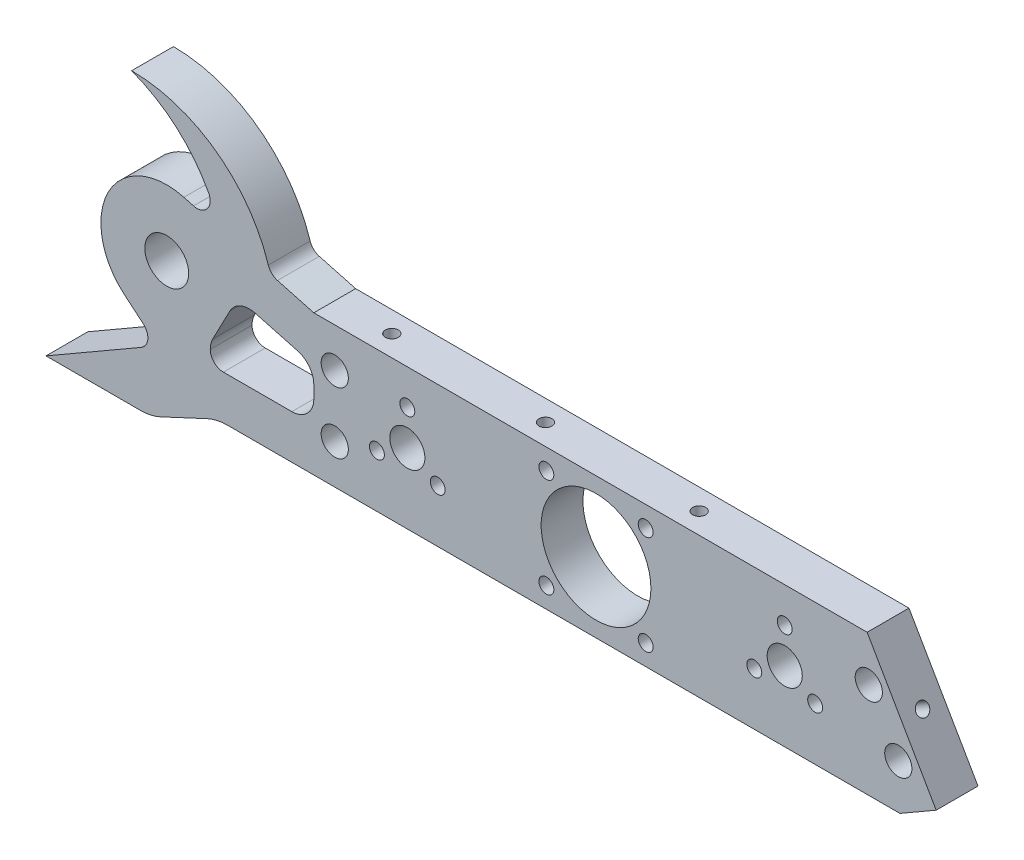
SolidWorks part; units mm, degrees
material "PE High Density"
ref_plane "Front Plane" through (0, 0, 0) normal (0, 0, 1) x (1, 0, 0)
ref_plane "Top Plane" through (0, 0, 0) normal (0, 1, 0) x (1, 0, 0)
ref_plane "Right Plane" through (0, 0, 0) normal (1, 0, 0) x (0, 0, -1)
sketch "Sketch1" plane through (0, 0, 0) normal (0, 0, 1) x (1, 0, 0)
  line L0 (-93.8686, 23.9824) -> (-64.275, 16)
  line L1 (-54.75, -16) -> (61.75, -16)
  line L2 (-54.75, -16) -> (-54.75, 16) construction
  line L3 (-54.75, 16) -> (61.75, 16)
  line L4 (61.75, -16) -> (61.75, 16)
  line L5 (-54.75, -16) -> (61.75, 16) construction
  line L6 (-54.75, 16) -> (61.75, -16) construction
  line L7 (-54.75, -16) -> (-90.7211, -16)
  line L8 (-90.7211, -16) -> (-107.4168, -1.9907)
  line L9 (-54.75, 16) -> (-64.275, 16)
  line L10 (-64.275, 16) -> (-64.275, -16) construction
  line L11 (-112.2407, -24) -> (26.8379, -24) construction
  line L12 (3.5, 0) -> (0, 0) construction
  arc A0 (-93.8686, 23.9824) -> (-107.4168, -1.9907) centre (-97.775, 9.5) ccw
  circle A1 centre (-97.775, 9.5) radius 5
  circle A2 centre (-97.775, 9.5) radius 33.5 construction
  circle A3 centre (3.5, 0) radius 24 construction
  point P0 (0, 0)
  dimension "D3" = 10
  dimension "D5" = 67
  dimension "D4" = 15
  dimension "D8" = 48
  dimension "D1" = 32
  dimension "D2" = 116.5
  dimension "D6" = 40
  dimension "D7" = 9.525
  dimension "D9" = 3.5
extrude "Initial Body" add sketch "Sketch1" along normal mid plane 9.525
sketch "Sketch2" plane through (0, 0, 4.7625) normal (0, 0, 1) x (1, 0, 0)
  circle A1 centre (0, 0) radius 12.5
  circle A2 centre (0, 0) radius 12.5
  circle A3 centre (-11.3137, 11.3137) radius 1.7
  circle A4 centre (-11.3137, 11.3137) radius 1.7
  circle A5 centre (-11.3137, -11.3137) radius 1.7
  circle A6 centre (-11.3137, -11.3137) radius 1.7
  circle A7 centre (11.3137, 11.3137) radius 1.7
  circle A8 centre (11.3137, 11.3137) radius 1.7
  circle A9 centre (11.3137, -11.3137) radius 1.7
  circle A10 centre (11.3137, -11.3137) radius 1.7
  circle A11 centre (49.9073, -4) radius 1.7
  circle A12 centre (49.9073, -4) radius 1.7
  circle A13 centre (42.9791, 8) radius 1.7
  circle A14 centre (42.9791, 8) radius 1.7
  circle A15 centre (36.0509, -4) radius 1.7
  circle A16 centre (36.0509, -4) radius 1.7
  circle A17 centre (42.9791, 0) radius 4
  circle A18 centre (42.9791, 0) radius 4
  circle A19 centre (-42.9791, 8) radius 1.7
  circle A20 centre (-42.9791, 8) radius 1.7
  circle A21 centre (-49.9073, -4) radius 1.7
  circle A22 centre (-49.9073, -4) radius 1.7
  circle A23 centre (-42.9791, 0) radius 4
  circle A24 centre (-42.9791, 0) radius 4
  circle A25 centre (-36.0509, -4) radius 1.7
  circle A26 centre (-36.0509, -4) radius 1.7
  dimension "D1" = 0
  dimension "D2" = 0
  dimension "D3" = 0
  dimension "D4" = 0
  dimension "D5" = 0
  dimension "D6" = 0
  dimension "D7" = 0
  dimension "D8" = 0
  dimension "D9" = 0
  dimension "D10" = 0
  dimension "D11" = 0
  dimension "D12" = 0
  dimension "D13" = 0
extrude "Drive Mounting Holes" cut sketch "Sketch2" against normal through all
fillet "Fillet1" radius 12 1 edges at (-90.7211, -16, 0)
sketch "Sketch3" plane through (0, 0, 4.7625) normal (0, 0, 1) x (1, 0, 0)
  line L0 (61.75, 16) -> (77.4756, -11.2375)
  line L1 (77.4756, -11.2375) -> (69.2267, -16)
  line L2 (69.2267, -16) -> (61.75, -16)
  line L3 (69.2267, -16) -> (61.75, -3.05) construction
  line L4 (61.75, -16) -> (61.75, 16) construction
  line L5 (61.75, -16) -> (61.75, 16)
  line L6 (61.75, -3.05) -> (53.5011, 11.2375) construction
  line L7 (53.5011, 11.2375) -> (61.75, 16) construction
  circle A0 centre (42.9791, 0) radius 12.5 construction
  dimension "D3" = 25
  dimension "D1" = 9.525
  dimension "D2" = 60
extrude "Backplate Mounting Protrusion" add sketch "Sketch3" against normal up to surface (9.525 mm away) up to face at (-41.2791, 8, -4.7625)
sketch "Sketch4" plane through (0, 0, 4.7625) normal (0, 0, 1) x (1, 0, 0)
  circle A0 centre (68.8511, -5.8245) radius 3.1 construction
  circle A1 centre (62.1256, 5.8245) radius 3.1 construction
  circle A2 centre (68.8511, -5.8245) radius 3.1
  circle A3 centre (62.1256, 5.8245) radius 3.1
extrude "Backplate Mounting Holes" cut sketch "Sketch4" against normal through all
sketch "Sketch5" plane through (0, 0, 4.7625) normal (0, 0, 1) x (1, 0, 0)
  circle A0 centre (-59.5125, -7) radius 3.1 construction
  circle A1 centre (-59.5125, 7) radius 3.1 construction
  circle A2 centre (-59.5125, -7) radius 3.1
  circle A3 centre (-59.5125, 7) radius 3.1
extrude "Frontplate Mounting Holes" cut sketch "Sketch5" against normal through all
sketch "Bottom" plane through (0, -16, 0) normal (0, -1, 0) x (1, 0, 0)
  line L0 (-86.3535, 0) -> (69.2267, 0) construction
  line L1 (-86.3535, 4.7625) -> (-86.3535, -4.7625) construction
  line L2 (69.2267, -4.7625) -> (69.2267, 4.7625) construction
  point P7 (54.2267, 0)
  dimension "D1" = 15
hole_wizard "#32 (0.116) Diameter Hole1" positions "Sketch7" profile "Sketch9" hole size "#32" standard "ANSI Inch"
sketch "Sketch7" plane through (0, -16, 0) normal (0, -1, 0) x (-1, 0, 0)
  point P0 (-54.2267, 0)
sketch "Sketch9" plane through (54.2267, -16, 0) normal (1, 0, 0) x (0, 0, -1)
  line L0 (0, 0) -> (0, 13.5852)
  line L1 (0, 13.5852) -> (1.4732, 12.7)
  line L2 (1.4732, 12.7) -> (1.4732, 0)
  line L5 (1.4732, 0) -> (0, 0)
  line L10 (0, 13.5852) -> (-1.4732, 12.7) construction
  line L11 (0, -6.35) -> (0, 107.95) construction
  dimension "Hole Dia." = 2.9464
  dimension "Hole Depth" = 12.7
  dimension "Drill Angle" = 118
pattern_linear "#32 Hole Pattern" count 4 spacing 36 along (-1, 0, 0) of "#32 (0.116) Diameter Hole1"
sketch "Sketch10" plane through (0, 16, 0) normal (0, 1, 0) x (1, 0, 0)
  line L0 (-64.275, 0) -> (61.75, 0) construction
  line L1 (-64.275, -4.7625) -> (-64.275, 4.7625) construction
  line L2 (61.75, -4.7625) -> (61.75, 4.7625) construction
  point P6 (-51.275, 0)
  dimension "D1" = 13
hole_wizard "#32 (0.116) Diameter Hole2" positions "Sketch11" profile "Sketch13" hole size "#32" standard "ANSI Inch"
sketch "Sketch11" plane through (0, 16, 0) normal (0, 1, 0) x (1, 0, 0)
  point P0 (-51.275, 0)
sketch "Sketch13" plane through (-51.275, 16, 0) normal (1, 0, 0) x (0, 0, 1)
  line L0 (0, 0) -> (0, 13.5852)
  line L1 (0, 13.5852) -> (1.4732, 12.7)
  line L2 (1.4732, 12.7) -> (1.4732, 0)
  line L5 (1.4732, 0) -> (0, 0)
  line L10 (0, 13.5852) -> (-1.4732, 12.7) construction
  line L11 (0, -6.35) -> (0, 107.95) construction
  dimension "Hole Dia." = 2.9464
  dimension "Hole Depth" = 12.7
  dimension "Drill Angle" = 118
pattern_linear "LPattern2" count 3 spacing 35 along (1, 0, 0) of "#32 (0.116) Diameter Hole2"
sketch "Sketch14" [suppressed] plane through (0, 0, 4.7625) normal (0, 0, 1) x (1, 0, 0)
  circle A0 centre (-97.775, 0) radius 1.7 construction
  circle A1 centre (-110.275, 9.5) radius 1.7 construction
  circle A2 centre (-97.775, 19) radius 1.7 construction
  circle A3 centre (-85.275, 9.5) radius 1.7 construction
  circle A4 centre (-97.775, 0) radius 1.7
  circle A5 centre (-110.275, 9.5) radius 1.7
  circle A6 centre (-97.775, 19) radius 1.7
  circle A7 centre (-85.275, 9.5) radius 1.7
extrude "Hubmotor Mounting Holes" [suppressed] cut sketch "Sketch14" against normal through all
sketch "Sketch15" plane through (0, 0, 4.7625) normal (0, 0, 1) x (1, 0, 0)
  circle A1 centre (-106.6634, 14.1364) radius 1.7
  circle A3 centre (-106.6634, 14.1364) radius 1.7 construction
extrude "Cut-Extrude2" [suppressed] cut sketch "Sketch15" against normal through all
pattern_circular "CirPattern1" [suppressed] count 3 over 360 of bodies 111
sketch "Sketch16" plane through (0, 0, 4.7625) normal (0, 0, 1) x (1, 0, 0)
  line L0 (-97.775, 9.5) -> (-85.3622, 3.0252) construction
  line L1 (-93.8964, -13.3356) -> (-76.828, 19.386) construction
  line L2 (-107.4168, -1.9907) -> (-94.0669, -13.1925) construction
  line L3 (-64.275, 16) -> (-93.8686, 23.9824) construction
  line L4 (-64.275, 16) -> (-64.275, -16) construction
  line L5 (-64.275, 16) -> (-64.275, -16) construction
  line L6 (-81.5643, 10.3061) -> (-89.1602, -4.2558)
  line L7 (-89.1602, -4.2558) -> (-87.0814, -6)
  line L8 (-87.0814, -6) -> (-64.275, -6)
  line L9 (-64.275, -6) -> (-64.275, 5.6426)
  line L10 (-64.275, 5.6426) -> (-81.5643, 10.3061)
  line L11 (-86.3535, -16) -> (69.2267, -16) construction
  line L12 (-87.0814, -6) -> (-86.3535, -4)
  line L13 (-75.6782, -6) -> (-75.6782, -16) construction
  line L14 (-72.9197, 7.9744) -> (-70.3154, 17.6293) construction
  line L15 (-88.1208, -5.1279) -> (-94.5487, -12.7883) construction
  circle A0 centre (-97.775, 9.5) radius 5 construction
  circle A1 centre (-97.775, 9.5) radius 5 construction
  arc A2 (-94.0669, -13.1925) -> (-86.3535, -16) centre (-86.3535, -4) ccw construction
  arc A3 (-94.0669, -13.1925) -> (-86.3535, -16) centre (-86.3535, -4) ccw construction
  dimension "D1" = 14
  dimension "D2" = 10
extrude "Cut-Extrude3" cut sketch "Sketch16" against normal through all contours L9 L10 L6 L7 L8 region at (-75.7442, 0.7431, 4.7625)
fillet "Fillet2" radius 5 5 edges at (-87.0814, -6, 0) (-81.5643, 10.3061, 0) (-64.275, 5.6426, 0) (-64.275, -6, 0) (-89.1602, -4.2558, 0)
fillet "Fillet3" radius 3 1 edges at (-87.1188, -5.6423, 0)
sketch "Sketch17" plane through (0, 0, 4.7625) normal (0, 0, 1) x (1, 0, 0)
  line L0 (-200112.2407, -24) -> (200026.8379, -24) construction
  line L1 (-200112.2407, -24) -> (200026.8379, -24) construction
  line L2 (-99.8635, -8.3287) -> (-125.275, -23)
  line L3 (-107.4168, -1.9907) -> (-94.0669, -13.1925) construction
  line L4 (-155.1286, -24) -> (-147.8608, -24) construction
  line L5 (-86.3535, -16) -> (-101.365, -23)
  line L6 (-86.3535, -16) -> (69.2267, -16) construction
  line L7 (-101.365, -23) -> (-125.275, -23)
  line L8 (-86.3535, -16) -> (-99.8635, -8.3287)
  circle A0 centre (3.5, 0) radius 24 construction
  circle A1 centre (-97.775, 9.5) radius 33.5 construction
  circle A2 centre (3.5, 0) radius 24 construction
  circle A3 centre (-97.775, 9.5) radius 33.5 construction
  point P13 (-131.275, 9.5)
  point P20 (-97.775, -24)
  dimension "D1" = 30
  dimension "D2" = 25
  dimension "D3" = 6
  dimension "D4" = 1
extrude "Boss-Extrude1" add sketch "Sketch17" against normal up to surface (9.525 mm away) up to face at (-76.2555, 0.865, -4.7625)
fillet "Fillet4" radius 11 2 edges at (-86.3535, -16, 0) (-101.365, -23, 0)
fillet "Fillet5" radius 3 1 edges at (-99.8635, -8.3287, 0)
sketch "Sketch18" plane through (0, 0, 4.7625) normal (0, 0, 1) x (1, 0, 0)
  line L0 (-93.8686, 23.9824) -> (-64.275, 16) construction
  line L1 (-118.9426, 43) -> (-72.8357, 43) construction
  line L2 (-74.1891, 18.6742) -> (-85.775, 21.7993)
  circle A0 centre (-97.775, 9.5) radius 33.5 construction
  circle A1 centre (-97.775, 9.5) radius 33.5 construction
  arc A2 (-85.775, 21.7993) -> (-105.775, 43) centre (-117.312, 12.0824) ccw
  arc A3 (-105.775, 43) -> (-74.1891, 18.6742) centre (-105.775, 10.3307) cw
  dimension "D1" = 8
  dimension "D4" = 33
  dimension "D2" = 12
  dimension "D3" = 12
extrude "Boss-Extrude2" add sketch "Sketch18" against normal up to surface (9.525 mm away) up to face at (-76.2555, 0.865, -4.7625)
fillet "Fillet6" radius 3 2 edges at (-74.1891, 18.6742, 0) (-85.775, 21.7993, 0)
sketch "Sketch19" plane through (53.2407, 30.7385, 0) normal (0.866, 0.5, 0) x (0, 0, -1)
  circle A0 centre (0, -32.7442) radius 1.95 construction
  circle A1 centre (0, -32.7442) radius 1.95 construction
  circle A2 centre (0, -32.7442) radius 1.475
  dimension "D1" = 2.95
extrude "Cut-Extrude4" cut sketch "Sketch19" against normal blind 9.525
equation "\"D2@Sketch1\"=120.00mm-\"D9@Sketch1\""
equation "\"D2\"= \"top_sidepanel_hole_spacing@A-0000-N - ROOT LOCUS.Assembly\""
equation "\"D1@Bottom\"= \"bottom_sidepanel_hole_offset@A-0000-N - ROOT LOCUS.Assembly\""
equation "\"D3@#32 Hole Pattern\"= \"bottom_sidepanel_hole_spacing@A-0000-N - ROOT LOCUS.Assembly\""
